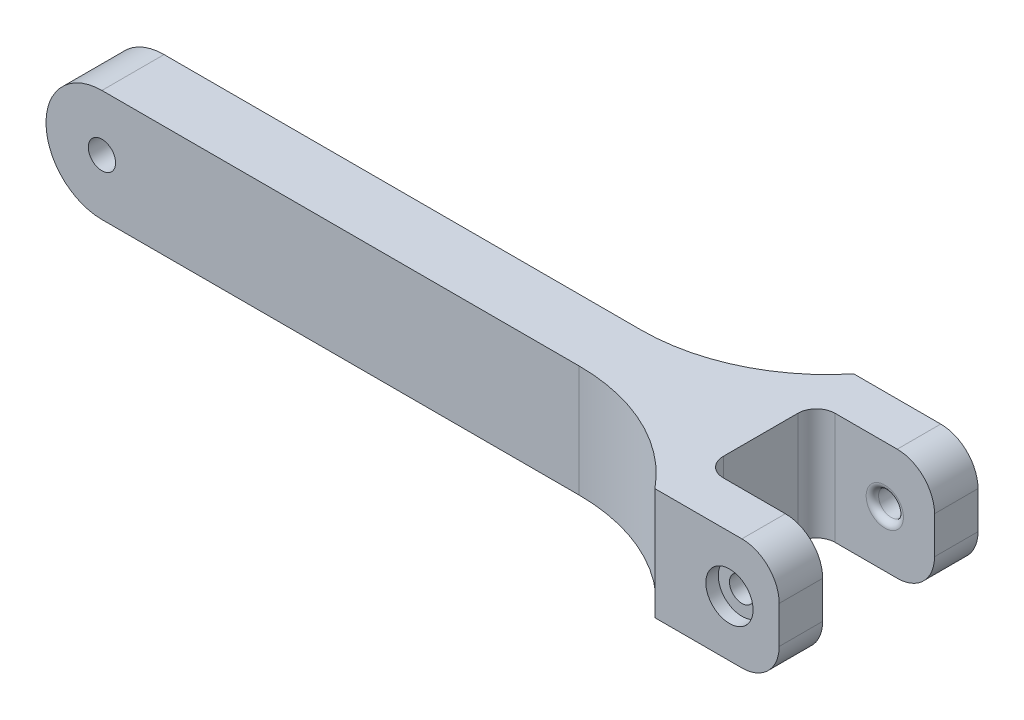
SolidWorks part; units mm, degrees
ref_plane "Front Plane" through (0, 0, 0) normal (0, 0, 1) x (1, 0, 0)
ref_plane "Top Plane" through (0, 0, 0) normal (0, 1, 0) x (1, 0, 0)
ref_plane "Right Plane" through (0, 0, 0) normal (1, 0, 0) x (0, 0, -1)
sketch "Sketch1" plane through (0, 0, 0) normal (0, 0, 1) x (1, 0, 0)
  line L0 (0, 0) -> (50, 0) construction
  line L1 (0, 4.5) -> (50, 4.5)
  line L2 (0, -4.5) -> (50, -4.5)
  line L3 (50, 4.5) -> (50, -4.5)
  circle A0 centre (0, 0) radius 1.1
  circle A2 centre (0, 0) radius 4.5
  dimension "D2" = 9
  dimension "D1" = 50
extrude "Boss-Extrude1" add sketch "Sketch1" along normal blind 5 contours A0 A2 | A2 L0 L1 | L0 A2 L2 region at (3.092, -3.092, 0) region at (26.7563, 2.2759, 0) region at (26.7563, -2.2759, 0)
sketch "Sketch2" plane through (0, 4.5, 0) normal (0, 1, 0) x (1, 0, 0)
  line L0 (50, -2.5) -> (60, -2.5) construction
  line L1 (50, -5) -> (50, 0) construction
  line L2 (60, 2) -> (50.5, 2)
  line L3 (50, 5.5) -> (60, 5.5)
  line L4 (50, 5.5) -> (50, -10.5)
  line L5 (50, -10.5) -> (60, -10.5)
  line L6 (60, 5.5) -> (60, -10.5)
  line L7 (50, 5.5) -> (60, -10.5) construction
  line L8 (50, -10.5) -> (60, 5.5) construction
  line L9 (50.5, 2) -> (50.5, -7)
  line L10 (50.5, -7) -> (60, -7)
  point P4 (55, -2.5)
  line M5 (50, -5) -> (50, 0)
  dimension "D1" = 16
  dimension "D2" = 3.5
  dimension "D3" = 9
  dimension "D4" = 10
  dimension "D5" = 9.5
  dimension "D6" = 10
  dimension "D7" = 10
extrude "Boss-Extrude2" add sketch "Sketch2" against normal blind 9 contours L10 L9 L2 L6 L3 L4 L5 M5 region at (55.25, 4.5, -2.1887)
fillet "Fillet1" radius 15 2 edges
sketch "Sketch3" plane through (0, 0, 10.5) normal (0, 0, 1) x (1, 0, 0)
  line L0 (50, 4.5) -> (60, 4.5) construction
  line L2 (50, -4.5) -> (50, 4.5) construction
  circle A0 centre (56, 0) radius 1
  dimension "D1" = 4.5
  dimension "D2" = 6
extrude "Cut-Extrude1" cut sketch "Sketch3" against normal blind 16
fillet "Fillet2" radius 3 4 edges at (60, 4.5, -3.75) (60, 4.5, 8.75) (60, -4.5, 8.75) (60, -4.5, -3.75)
sketch "Sketch4" plane through (0, 0, 10.5) normal (0, 0, 1) x (1, 0, 0)
  circle A0 centre (56, 0) radius 1.9
extrude "Cut-Extrude2" cut sketch "Sketch4" against normal blind 1
fillet "Fillet3" radius 1.5 2 edges at (50.5, 0, 7) (50.5, 0, -2)
fillet "Fillet4" radius 0.5 1 edges at (55, 0, -2)
